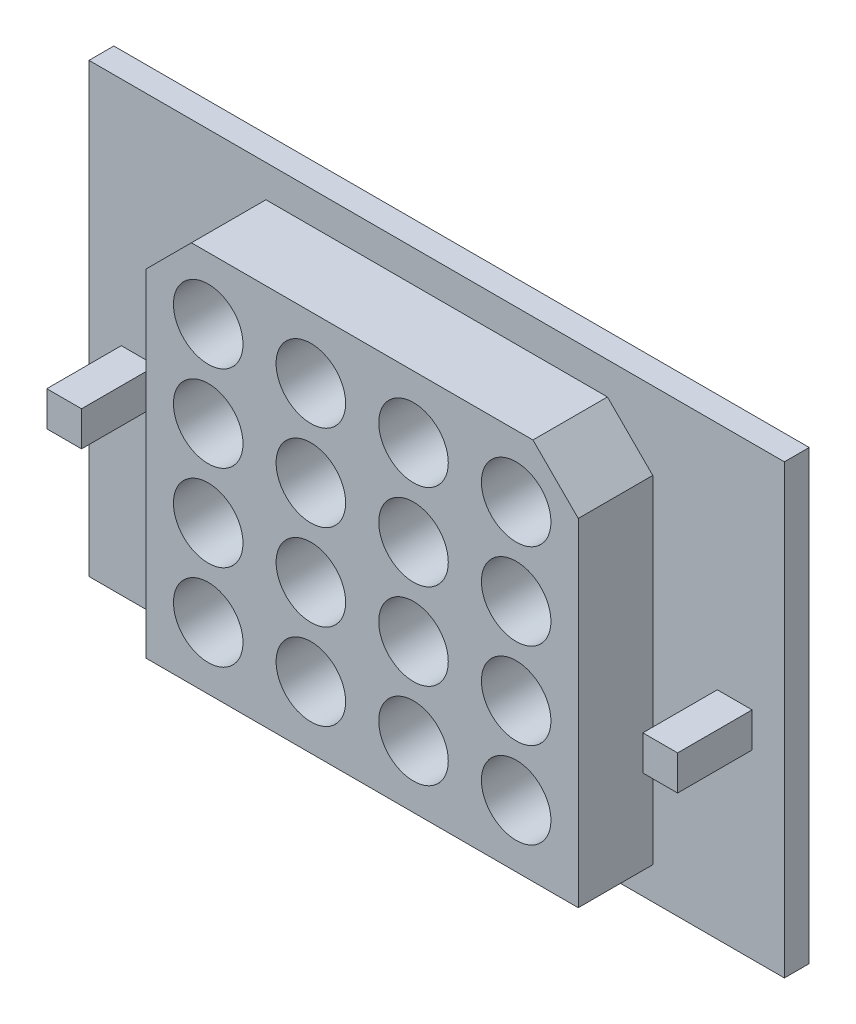
SolidWorks part; units mm, degrees
ref_plane "Front Plane" through (0, 0, 0) normal (0, 0, 1) x (1, 0, 0)
ref_plane "Top Plane" through (0, 0, 0) normal (0, 1, 0) x (1, 0, 0)
ref_plane "Right Plane" through (0, 0, 0) normal (1, 0, 0) x (0, 0, -1)
sketch "Sketch1" plane through (0, 0, 0) normal (0, 0, 1) x (1, 0, 0)
  line L1 (-15.2366, 7.7588) -> (12.7634, 7.7588)
  line L2 (-15.2366, 7.7588) -> (-15.2366, -10.2412)
  line L3 (-15.2366, -10.2412) -> (12.7634, -10.2412)
  line L4 (12.7634, 7.7588) -> (12.7634, -10.2412)
  dimension "D1" = 28
  dimension "D2" = 18
extrude "Boss-Extrude1" add sketch "Sketch1" along normal blind 1
sketch "Sketch2" plane through (0, 0, 1) normal (0, 0, 1) x (1, 0, 0)
  line L0 (-1.2366, 7.7588) -> (-1.2366, -10.2412) construction
  line L1 (12.7634, 7.7588) -> (-15.2366, 7.7588) construction
  line L2 (-15.2366, -10.2412) -> (12.7634, -10.2412) construction
  line L3 (-15.2366, -1.2412) -> (12.7634, -1.2412) construction
  line L4 (-15.2366, 7.7588) -> (-15.2366, -10.2412) construction
  line L5 (12.7634, -10.2412) -> (12.7634, 7.7588) construction
  line L7 (-14.2366, -1.2412) -> (-12.2366, -1.2412) construction
  line L8 (-14.2366, -1.2412) -> (-14.2366, -3.2412) construction
  line L9 (-14.2366, -3.2412) -> (-12.2366, -3.2412) construction
  line L10 (-12.2366, -1.2412) -> (-12.2366, -3.2412) construction
  line L11 (11.7634, -1.2412) -> (9.7634, -1.2412) construction
  line L12 (11.7634, -1.2412) -> (11.7634, -3.2412) construction
  line L13 (11.7634, -3.2412) -> (9.7634, -3.2412) construction
  line L14 (9.7634, -1.2412) -> (9.7634, -3.2412) construction
  line L15 (-10.2366, 6.7588) -> (7.7634, 6.7588) construction
  line L16 (-10.2366, 6.7588) -> (-10.2366, -9.2412) construction
  line L17 (-10.2366, -9.2412) -> (7.7634, -9.2412) construction
  line L18 (7.7634, 6.7588) -> (7.7634, -9.2412) construction
  line L22 (11.4634, -1.5412) -> (10.0634, -1.5412)
  line L23 (10.0634, -1.5412) -> (10.0634, -2.9412)
  line L24 (11.4634, -2.9412) -> (10.0634, -2.9412)
  line L25 (11.4634, -1.5412) -> (11.4634, -2.9412)
  line L30 (-13.9366, -1.5412) -> (-12.5366, -1.5412)
  line L31 (-12.5366, -1.5412) -> (-12.5366, -2.9412)
  line L32 (-13.9366, -2.9412) -> (-12.5366, -2.9412)
  line L33 (-13.9366, -1.5412) -> (-13.9366, -2.9412)
  line L34 (5.7634, 6.7588) -> (7.7634, 4.7588) construction
  line L35 (-10.2366, 4.7588) -> (-8.2366, 6.7588) construction
  line L36 (-8.1124, 6.4588) -> (5.6391, 6.4588)
  line L37 (7.4634, 4.6345) -> (7.4634, -8.9412)
  line L38 (-9.9366, -8.9412) -> (7.4634, -8.9412)
  line L39 (-9.9366, 4.6345) -> (-9.9366, -8.9412)
  line L40 (-9.9366, 4.6345) -> (-8.1124, 6.4588)
  line L41 (5.6391, 6.4588) -> (7.4634, 4.6345)
  line L42 (7.4634, 6.4588) -> (7.4634, -8.9412) construction
  line L43 (-9.9366, 6.4588) -> (7.4634, 6.4588) construction
  line L44 (-9.9366, 6.4588) -> (-9.9366, -8.9412) construction
  line L45 (-10.0245, 4.5466) -> (-8.0245, 6.5466) construction
  line L46 (5.5512, 6.5466) -> (7.5512, 4.5466) construction
  point P26 (-1.2366, 6.7588)
  point P27 (-10.2366, -1.2412)
  dimension "D1" = 2
  dimension "D2" = 2
  dimension "D3" = 6
  dimension "D4" = 2
  dimension "D5" = 2
  dimension "D6" = 6
  dimension "D7" = 18
  dimension "D8" = 16
  dimension "D9" = 0
  dimension "D10" = 0
  dimension "D12" = 2
  dimension "D13" = 2
  dimension "D11" = 135
  dimension "D16" = 135
  dimension "D17" = 2
  dimension "D18" = 2
  dimension "D14" = 0.3
  dimension "D15" = 0.3
  dimension "D19" = 0.3
  dimension "D20" = 0.3
extrude "Boss-Extrude3" add sketch "Sketch2" along normal blind 3
sketch "Sketch3" plane through (0, 0, 4) normal (0, 0, 1) x (1, 0, 0)
  line L0 (5.6391, 6.4588) -> (-8.1124, 6.4588) construction
  line L1 (-9.9366, 4.6345) -> (-9.9366, -8.9412) construction
  line L2 (7.4634, -8.9412) -> (7.4634, 4.6345) construction
  line L4 (-9.9366, -8.9412) -> (7.4634, -8.9412) construction
  circle A0 centre (-7.4366, 3.9588) radius 1.4
  circle A1 centre (-3.3033, 3.9588) radius 1.4
  circle A2 centre (0.83, 3.9588) radius 1.4
  circle A3 centre (4.9634, 3.9588) radius 1.4
  circle A4 centre (-3.3033, 0.4921) radius 1.4
  circle A5 centre (0.83, 0.4921) radius 1.4
  circle A6 centre (4.9634, 0.4921) radius 1.4
  circle A7 centre (-3.3033, -2.9746) radius 1.4
  circle A8 centre (0.83, -2.9746) radius 1.4
  circle A9 centre (4.9634, -2.9746) radius 1.4
  circle A10 centre (-3.3033, -6.4412) radius 1.4
  circle A11 centre (0.83, -6.4412) radius 1.4
  circle A12 centre (4.9634, -6.4412) radius 1.4
  circle A13 centre (-7.4366, 0.4921) radius 1.4
  circle A14 centre (-7.4366, -2.9746) radius 1.4
  circle A15 centre (-7.4366, -6.4412) radius 1.4
  dimension "D2" = 2.8
  dimension "D1" = 2.5
  dimension "D3" = 2.5
  dimension "D4" = 2.5
  dimension "D5" = 2.5
  dimension "D6" = 2.5
  dimension "D7" = 4
  dimension "D8" = 4
extrude "Cut-Extrude1" cut sketch "Sketch3" against normal blind 10
